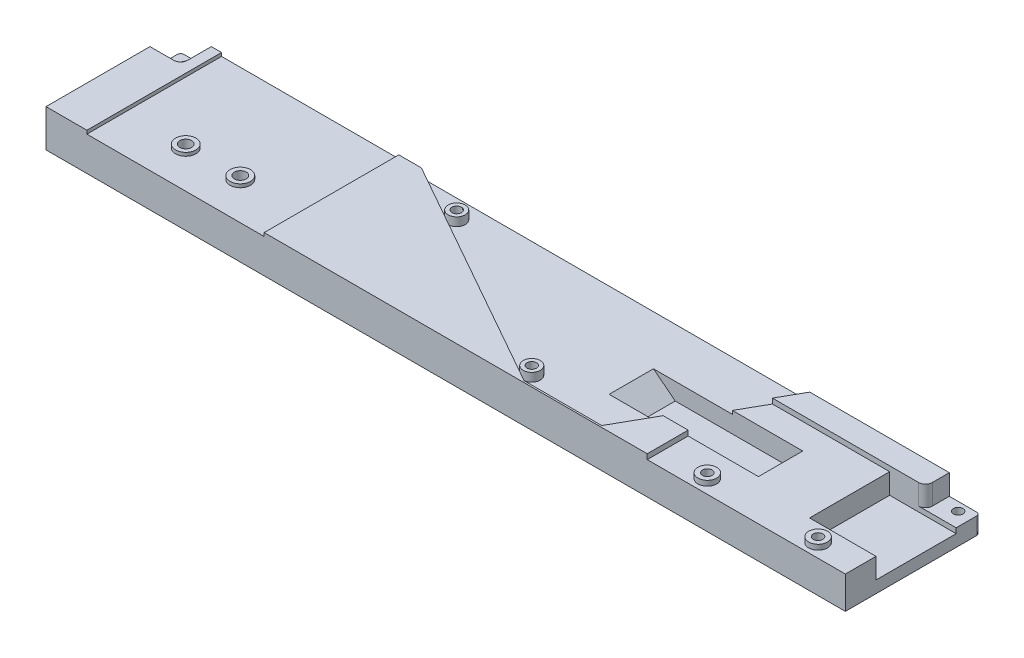
SolidWorks part; units mm, degrees
ref_plane "前视基准面" through (0, 0, 0) normal (0, 0, 1) x (1, 0, 0)
ref_plane "上视基准面" through (0, 0, 0) normal (0, 1, 0) x (1, 0, 0)
ref_plane "右视基准面" through (0, 0, 0) normal (1, 0, 0) x (0, 0, -1)
sketch "草图1" plane through (0, 0, 0) normal (0, 1, 0) x (1, 0, 0)
  line L1 (-16.4884, 7.0754) -> (218.0116, 7.0754)
  line L2 (-16.4884, 7.0754) -> (-16.4884, -32.4246)
  line L3 (-16.4884, -32.4246) -> (218.0116, -32.4246)
  line L4 (218.0116, 7.0754) -> (218.0116, -32.4246)
  dimension "D1" = 234.5
  dimension "D2" = 39.5
extrude "凸台-拉伸1" add sketch "草图1" along normal blind 11
sketch "草图2" plane through (0, 11, 0) normal (0, 1, 0) x (1, 0, 0)
  line L1 (-16.4884, 7.0754) -> (-7.4884, 7.0754)
  line L2 (-16.4884, 7.0754) -> (-16.4884, -1.9246)
  line L3 (-16.4884, -1.9246) -> (-7.4884, -1.9246)
  line L4 (-7.4884, 7.0754) -> (-7.4884, -1.9246)
  line L5 (218.0116, 7.0754) -> (209.0116, 7.0754)
  line L6 (218.0116, 7.0754) -> (218.0116, 0.0754)
  line L7 (218.0116, 0.0754) -> (209.0116, 0.0754)
  line L8 (209.0116, 7.0754) -> (209.0116, 0.0754)
  dimension "D1" = 9
  dimension "D2" = 7
  dimension "D3" = 9
  dimension "D4" = 9
extrude "切除-拉伸1" cut sketch "草图2" against normal blind 6
fillet "圆角2" radius 2 2 edges at (-7.4884, 8, 1.9246) (209.0116, 8, -0.0754)
sketch "草图3" plane through (0, 5, 0) normal (0, 1, 0) x (1, 0, 0)
  line L0 (218.0116, 0.0754) -> (218.0116, 7.0754) construction
  line L1 (-16.4884, 7.0754) -> (-16.4884, -1.9246) construction
  circle A0 centre (214.1116, 4.5754) radius 1.4
  circle A2 centre (-12.5884, 4.5754) radius 1.4
  dimension "D1" = 2.8
  dimension "D2" = 2.8
  dimension "D3" = 3.9
  dimension "D4" = 3.9
extrude "切除-拉伸2" cut sketch "草图3" against normal blind 6
fillet "圆角5" radius 1 2 edges at (218.0116, 2.5, -7.0754) (-16.4884, 2.5, -7.0754)
sketch "草图4" plane through (0, 11, 0) normal (0, 1, 0) x (1, 0, 0)
  line L0 (-16.4884, -32.4246) -> (218.0116, -32.4246) construction
  line L1 (218.0116, -32.4246) -> (218.0116, 0.0754) construction
  circle A0 centre (206.0116, -28.4246) radius 1.4
  circle A1 centre (173.5116, -28.4246) radius 1.4
  dimension "D3" = 2.8
  dimension "D4" = 2.8
  dimension "D1" = 4
  dimension "D2" = 4
  dimension "D5" = 32.5
  dimension "D6" = 12
extrude "切除-拉伸3" cut sketch "草图4" against normal blind 30
sketch "草图6" plane through (0, 11, 0) normal (0, 1, 0) x (1, 0, 0)
  line L0 (218.0116, -32.4246) -> (218.0116, 0.0754) construction
  line L1 (218.0116, 0.0754) -> (198.5116, 0.0754)
  line L2 (218.0116, 0.0754) -> (218.0116, -23.4246)
  line L3 (218.0116, -23.4246) -> (198.5116, -23.4246)
  line L4 (198.5116, 0.0754) -> (198.5116, -23.4246)
  line L5 (211.0116, 0.0754) -> (218.0116, 0.0754) construction
  circle A0 centre (206.0116, -28.4246) radius 1.4 construction
  dimension "D1" = 7.5
  dimension "D2" = 0
  dimension "D3" = 0
  dimension "D4" = 5
extrude "切除-拉伸4" cut sketch "草图6" against normal blind 7.5 contours L1 L4 L3 L2
fillet "圆角7" radius 2 1 edges at (211.0116, 8, -0.0754)
sketch "草图7" plane through (0, 11, 0) normal (0, 1, 0) x (1, 0, 0)
  line L1 (143.5116, -7.4246) -> (180.5116, -7.4246)
  line L2 (143.5116, -7.4246) -> (143.5116, -20.4246)
  line L3 (143.5116, -20.4246) -> (180.5116, -20.4246)
  line L4 (180.5116, -7.4246) -> (180.5116, -20.4246)
  circle A0 centre (173.5116, -28.4246) radius 1.4 construction
  dimension "D1" = 8
  dimension "D2" = 13
  dimension "D3" = 7
  dimension "D4" = 37
extrude "切除-拉伸5" cut sketch "草图7" against normal blind 7.5
chamfer "倒角1" distance 10 angle 38 1 edges at (143.5116, 11, 13.9246) first distance on face at (162.0116, 11, 13.9246)
sketch "草图8" plane through (0, 11, 0) normal (0, 1, 0) x (1, 0, 0)
  line L0 (-16.4884, -32.4246) -> (218.0116, -32.4246) construction
  line L1 (209.0116, 7.0754) -> (-7.4884, 7.0754) construction
  line L6 (133.5116, -20.4246) -> (133.5116, -7.4246) construction
  circle A0 centre (120.5116, -26.9246) radius 1.4
  circle A1 centre (69.9967, 1.5754) radius 1.4
  dimension "D1" = 2.8
  dimension "D2" = 5.5
  dimension "D3" = 2.8
  dimension "D4" = 5.5
  dimension "D5" = 58
  dimension "D7" = 13
extrude "切除-拉伸6" cut sketch "草图8" against normal blind 37.5
sketch "草图9" plane through (0, 11, 0) normal (0, 1, 0) x (1, 0, 0)
  line L0 (51.1037, 8.7901) -> (123.2686, -31.9246)
  line L1 (51.1037, 8.7901) -> (77.8719, 56.2355)
  line L2 (123.2686, -31.9246) -> (150.0368, 15.5207)
  line L3 (77.8719, 56.2355) -> (150.0368, 15.5207)
  line L4 (-16.4884, -32.4246) -> (218.0116, -32.4246) construction
  circle A0 centre (69.9967, 1.5754) radius 1.4 construction
  circle A1 centre (120.5116, -26.9246) radius 1.4 construction
  dimension "D5" = 3
  dimension "D1" = 90
  dimension "D2" = 20
  dimension "D3" = 3
  dimension "D4" = 54.4757
  dimension "D6" = 0.5
extrude "切除-拉伸8" cut sketch "草图9" against normal blind 2.5 contours L1 L3 L2 L0
sketch "草图10" plane through (0, 11, 0) normal (0, 1, 0) x (1, 0, 0)
  line L0 (-16.4884, -32.4246) -> (218.0116, -32.4246) construction
  line L2 (-16.4884, -1.9246) -> (-16.4884, -32.4246) construction
  circle A0 centre (13.5116, -21.4246) radius 1.75
  circle A1 centre (29.5116, -21.4246) radius 1.75
  dimension "D1" = 3.5
  dimension "D2" = 3.5
  dimension "D5" = 46
  dimension "D3" = 16
  dimension "D4" = 11
  dimension "D6" = 11
extrude "切除-拉伸9" cut sketch "草图10" against normal blind 13.5
sketch "草图11" plane through (0, 11, 0) normal (0, 1, 0) x (1, 0, 0)
  line L1 (-4.4884, 15.5754) -> (47.5116, 15.5754)
  line L2 (-4.4884, 15.5754) -> (-4.4884, -32.4246)
  line L3 (-4.4884, -32.4246) -> (47.5116, -32.4246)
  line L4 (47.5116, 15.5754) -> (47.5116, -32.4246)
  circle A0 centre (29.5116, -21.4246) radius 1.75 construction
  dimension "D4" = 18
  dimension "D1" = 52
  dimension "D2" = 48
  dimension "D3" = 11
extrude "切除-拉伸10" cut sketch "草图11" against normal blind 1
sketch "草图12" plane through (0, 10, 0) normal (0, 1, 0) x (1, 0, 0)
  circle A0 centre (13.5116, -21.4246) radius 3
  circle A1 centre (13.5116, -21.4246) radius 1.75
  circle A3 centre (29.5116, -21.4246) radius 3
  circle A4 centre (29.5116, -21.4246) radius 1.75
  dimension "D1" = 3.5
  dimension "D2" = 6
  dimension "D3" = 6
  dimension "D4" = 3.5
extrude "凸台-拉伸2" add sketch "草图12" along normal blind 1
sketch "草图13" plane through (0, 8.5, 0) normal (0, 1, 0) x (1, 0, 0)
  circle A0 centre (69.9967, 1.5754) radius 1.4
  circle A1 centre (69.9967, 1.5754) radius 2.5
  circle A3 centre (120.5116, -26.9246) radius 1.4
  circle A4 centre (120.5116, -26.9246) radius 2.5
  dimension "D1" = 5
  dimension "D2" = 5
  dimension "D3" = 2.8
  dimension "D4" = 2.8
extrude "凸台-拉伸3" add sketch "草图13" along normal blind 2.5
sketch "草图14" plane through (0, 11, 0) normal (0, 1, 0) x (1, 0, 0)
  line L0 (207.0116, 0.0754) -> (198.5116, 0.0754) construction
  line L1 (159.8893, 0.0754) -> (218.0116, 0.0754)
  line L2 (159.8893, 0.0754) -> (159.8893, -32.4246)
  line L3 (159.8893, -32.4246) -> (218.0116, -32.4246)
  line L4 (218.0116, 0.0754) -> (218.0116, -32.4246)
  line L5 (218.0116, -32.4246) -> (218.0116, -23.4246) construction
  line L6 (47.5116, -32.4246) -> (218.0116, -32.4246) construction
  dimension "D1" = 0
  dimension "D2" = 0
  dimension "D3" = 0
extrude "切除-拉伸11" cut sketch "草图14" against normal blind 1.5
sketch "草图15" plane through (0, 9.5, 0) normal (0, 1, 0) x (1, 0, 0)
  circle A0 centre (173.5116, -28.4246) radius 1.4
  circle A1 centre (173.5116, -28.4246) radius 2.75
  circle A2 centre (206.0116, -28.4246) radius 1.4
  circle A3 centre (206.0116, -28.4246) radius 2.75
  dimension "D1" = 5.5
  dimension "D2" = 5.5
  dimension "D3" = 2.8
  dimension "D4" = 2.8
extrude "凸台-拉伸4" add sketch "草图15" along normal blind 1.5
sketch "草图16" plane through (0, 11, 0) normal (0, 1, 0) x (1, 0, 0)
  line L0 (123.2686, -31.9246) -> (146.0666, -31.9246)
  line L1 (123.2686, -31.9246) -> (145.272, 7.0754)
  line L2 (146.0666, -31.9246) -> (168.07, 7.0754)
  line L3 (145.272, 7.0754) -> (168.07, 7.0754)
  line L4 (209.0116, 7.0754) -> (145.272, 7.0754) construction
  line L5 (137.0913, -7.4246) -> (145.272, 7.0754) construction
  dimension "D1" = 180
  dimension "D2" = 0
extrude "切除-拉伸12" cut sketch "草图16" against normal blind 2.5
